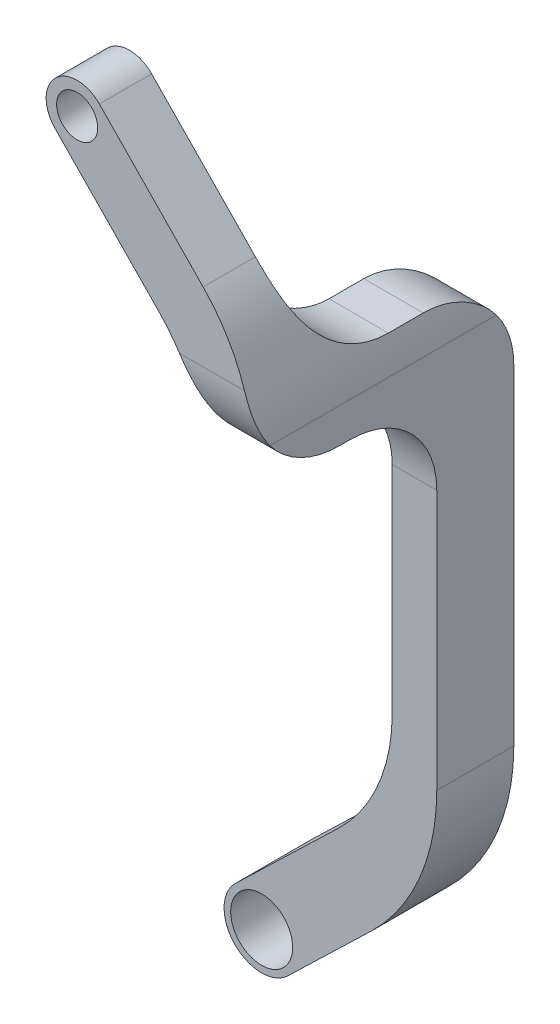
SolidWorks part; units mm, degrees
ref_plane "前视基准面" through (0, 0, 0) normal (0, 0, 1) x (1, 0, 0)
ref_plane "上视基准面" through (0, 0, 0) normal (0, 1, 0) x (1, 0, 0)
ref_plane "右视基准面" through (0, 0, 0) normal (1, 0, 0) x (0, 0, -1)
sketch "草图1" plane through (0, 0, 0) normal (0, 0, 1) x (1, 0, 0)
  line L0 (-35.5227, 95.2514) -> (24.0476, 34.0588)
  line L1 (-61.0316, 70.4188) -> (-1.4613, 9.2262)
  line L2 (26.7935, -60.304) -> (26.7935, -229.704)
  line L3 (52.3935, -35.6957) -> (52.3935, -254.9957)
  line L4 (-3.793, -301.6885) -> (-63.1081, -358.8852)
  line L7 (14.6503, -343.8232) -> (-33.1683, -389.934)
  circle A0 centre (-48.2772, 82.8351) radius 11.8
  arc A1 (-35.5227, 95.2514) -> (-61.0316, 70.4188) centre (-48.2772, 82.8351) ccw
  arc A2 (-1.4613, 9.2262) -> (26.7935, -60.304) centre (-72.885, -60.304) cw
  arc A3 (24.0476, 34.0588) -> (52.3935, -35.6957) centre (-47.6065, -35.6957) cw
  arc A4 (26.7935, -229.704) -> (-3.793, -301.6885) centre (-73.2065, -229.704) cw
  arc A5 (52.3935, -254.9957) -> (14.6503, -343.8232) centre (-71.0048, -254.9957) cw
  arc A6 (-63.1081, -358.8852) -> (-33.1683, -389.934) centre (-48.1382, -374.4096) ccw
  circle A7 centre (-48.1382, -374.4096) radius 17.8
  dimension "D2" = 23.6
  dimension "D4" = 100
  dimension "D7" = 100
  dimension "D9" = 35.6
  dimension "D11" = 17.8
  dimension "D1" = 85.4
  dimension "D3" = 85.4
  dimension "D5" = 219.3
  dimension "D6" = 169.4
  dimension "D8" = 82.4
  dimension "D10" = 25.6
extrude "凸台-拉伸2" add sketch "草图1" along normal mid plane 150
sketch "草图2" plane through (0, 0, 0) normal (1, 0, 0) x (0, 0, -1)
  line L0 (-75, 34.0588) -> (-75, -35.6957) construction
  line L1 (304.9, 915.9043) -> (-45, 915.9043)
  line L2 (304.9, 915.9043) -> (304.9, -15.6957)
  line L3 (304.9, -15.6957) -> (-45, -15.6957)
  line L4 (-45, 915.9043) -> (-45, -15.6957)
  line L5 (-241.4233, -55.6957) -> (30.7767, -55.6957)
  line L6 (-241.4233, -55.6957) -> (-241.4233, -1994.8957)
  line L7 (-241.4233, -1994.8957) -> (30.7767, -1994.8957)
  line L8 (30.7767, -55.6957) -> (30.7767, -1994.8957)
  line L9 (-75, -35.6957) -> (75, -35.6957) construction
  point P10 (-75, -0.8185)
  dimension "D1" = 30
  dimension "D2" = 931.6
  dimension "D3" = 349.9
  dimension "D4" = 1939.2
  dimension "D5" = 272.2
  dimension "D6" = 20
  dimension "D7" = 20
extrude "切除-拉伸1" cut sketch "草图2" against normal through all both and the other way through all
fillet "圆角1" radius 50 4 edges at (33.3139, -15.6957, 45) (39.5402, -55.6957, 75) (39.5402, -55.6957, -30.7767) (33.3139, -15.6957, -75)
equation "\"D7@草图2\"=\"D6@草图2\""
